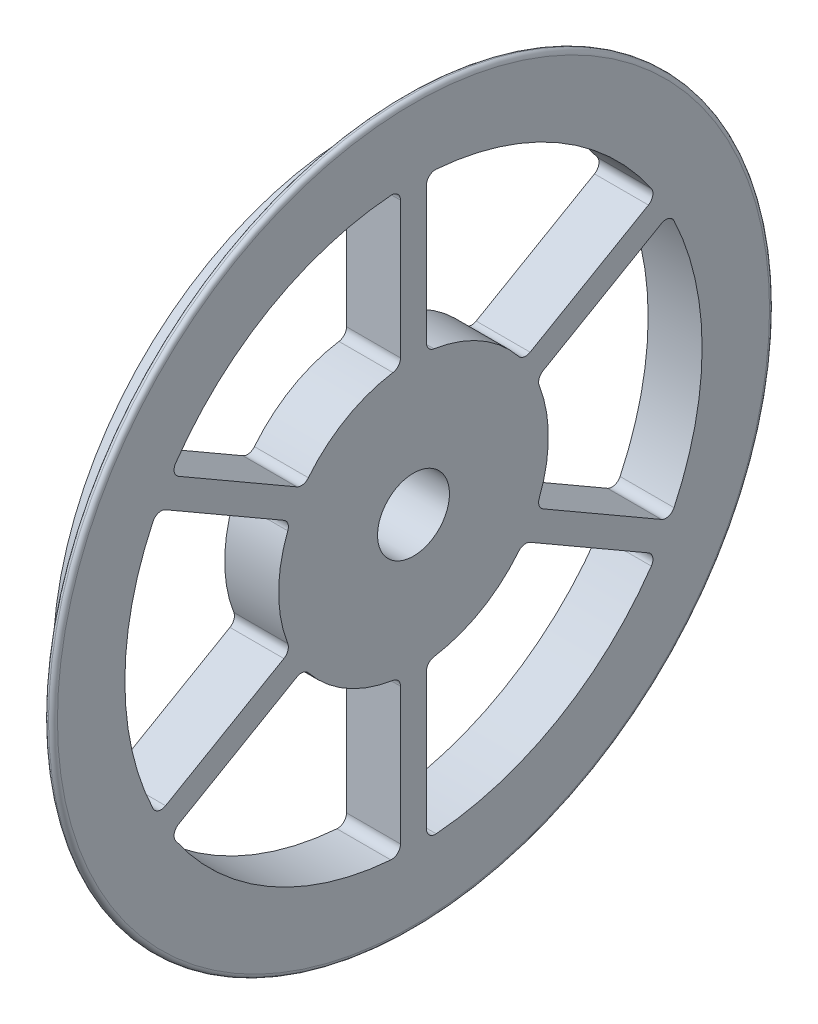
SolidWorks part; units mm, degrees
ref_plane "Front Plane" through (0, 0, 0) normal (0, 0, 1) x (1, 0, 0)
ref_plane "Top Plane" through (0, 0, 0) normal (0, 1, 0) x (1, 0, 0)
ref_plane "Right Plane" through (0, 0, 0) normal (1, 0, 0) x (0, 0, -1)
sketch "Sketch1" plane through (0, 0, 0) normal (0, 0, 1) x (1, 0, 0)
  line L2 (-3, 0) -> (-3, 38.05)
  line L5 (-3, 38.05) -> (2, 38.05)
  line L14 (2, 38.05) -> (2, 40.1)
  line L15 (2, 40.1) -> (3, 40.1)
  line L16 (3, 40.1) -> (3, 0)
  line L17 (3, 0) -> (-3, 0)
  dimension "D3" = 40.1
  dimension "D1" = 1
  dimension "D2" = 5
  dimension "D4" = 38.05
revolve "Revolve2" add sketch "Sketch1" angle 360 about L17
sketch "Sketch2" plane through (3, 0, 0) normal (-1, 0, 0) x (0, 0, 1)
  line L0 (0, 0) -> (13.6518, 0) construction
  line L1 (14.4156, 6.6562) -> (27.5718, 14.2519)
  line L2 (13.6518, 6.2152) -> (13.6518, -6.2152) construction
  line L3 (14.4156, -6.6562) -> (27.5718, -14.2519)
  line L4 (28.493, 14.7838) -> (28.493, -14.7838) construction
  line L5 (2.8868, 0) -> (13.6518, 6.2152) construction
  line L6 (2.8868, 0) -> (1.4434, 2.5) construction
  line L7 (1.4434, 2.5) -> (-1.4434, 2.5) construction
  line L8 (-1.4434, 2.5) -> (-2.8868, 0) construction
  line L9 (-2.8868, 0) -> (-1.4434, -2.5) construction
  line L10 (-1.4434, -2.5) -> (1.4434, -2.5) construction
  line L11 (1.4434, -2.5) -> (2.8868, 0) construction
  line L12 (13.6518, 0) -> (28.493, 0) construction
  line L13 (13.6518, -6.2152) -> (2.8868, 0) construction
  line L14 (12.9722, -9.1562) -> (26.1285, -16.7519)
  line L15 (1.4434, -15.8123) -> (1.4434, -31.0039)
  line L16 (-1.4434, -15.8123) -> (-1.4434, -31.0039)
  line L17 (-12.9722, -9.1562) -> (-26.1285, -16.7519)
  line L18 (-14.4156, -6.6562) -> (-27.5718, -14.2519)
  line L19 (-14.4156, 6.6562) -> (-27.5718, 14.2519)
  line L20 (-12.9722, 9.1562) -> (-26.1285, 16.7519)
  line L21 (-1.4434, 15.8123) -> (-1.4434, 31.0039)
  line L22 (1.4434, 15.8123) -> (1.4434, 31.0039)
  line L23 (12.9722, 9.1562) -> (26.1285, 16.7519)
  arc A0 (28.9745, 13.8163) -> (28.9745, -13.8163) centre (0, 0) cw
  circle A2 centre (0, 0) radius 2.5 construction
  arc A3 (13.9833, 5.4283) -> (13.9833, -5.4283) centre (0, 0) cw
  arc A4 (13.9833, -5.4283) -> (14.4156, -6.6562) centre (14.9156, -5.7901) ccw
  arc A5 (14.4156, 6.6562) -> (13.9833, 5.4283) centre (14.9156, 5.7901) ccw
  arc A6 (27.5718, -14.2519) -> (28.9745, -13.8163) centre (28.0718, -13.3859) ccw
  arc A7 (28.9745, 13.8163) -> (27.5718, 14.2519) centre (28.0718, 13.3859) ccw
  arc A8 (26.4525, -18.1845) -> (26.1285, -16.7519) centre (25.6285, -17.618) ccw
  arc A9 (26.4525, -18.1845) -> (2.5219, -32.0008) centre (0, 0) cw
  arc A10 (1.4434, -31.0039) -> (2.5219, -32.0008) centre (2.4434, -31.0039) ccw
  arc A11 (2.2907, -14.8241) -> (1.4434, -15.8123) centre (2.4434, -15.8123) ccw
  arc A12 (11.6927, -9.3958) -> (2.2907, -14.8241) centre (0, 0) cw
  arc A13 (12.9722, -9.1562) -> (11.6927, -9.3958) centre (12.4722, -10.0222) ccw
  arc A14 (-2.5219, -32.0008) -> (-1.4434, -31.0039) centre (-2.4434, -31.0039) ccw
  arc A15 (-2.5219, -32.0008) -> (-26.4525, -18.1845) centre (0, 0) cw
  arc A16 (-26.1285, -16.7519) -> (-26.4525, -18.1845) centre (-25.6285, -17.618) ccw
  arc A17 (-11.6927, -9.3958) -> (-12.9722, -9.1562) centre (-12.4722, -10.0222) ccw
  arc A18 (-2.2907, -14.8241) -> (-11.6927, -9.3958) centre (0, 0) cw
  arc A19 (-1.4434, -15.8123) -> (-2.2907, -14.8241) centre (-2.4434, -15.8123) ccw
  arc A20 (-28.9745, -13.8163) -> (-27.5718, -14.2519) centre (-28.0718, -13.3859) ccw
  arc A21 (-28.9745, -13.8163) -> (-28.9745, 13.8163) centre (0, 0) cw
  arc A22 (-27.5718, 14.2519) -> (-28.9745, 13.8163) centre (-28.0718, 13.3859) ccw
  arc A23 (-13.9833, 5.4283) -> (-14.4156, 6.6562) centre (-14.9156, 5.7901) ccw
  arc A24 (-13.9833, -5.4283) -> (-13.9833, 5.4283) centre (0, 0) cw
  arc A25 (-14.4156, -6.6562) -> (-13.9833, -5.4283) centre (-14.9156, -5.7901) ccw
  arc A26 (-26.4525, 18.1845) -> (-26.1285, 16.7519) centre (-25.6285, 17.618) ccw
  arc A27 (-26.4525, 18.1845) -> (-2.5219, 32.0008) centre (0, 0) cw
  arc A28 (-1.4434, 31.0039) -> (-2.5219, 32.0008) centre (-2.4434, 31.0039) ccw
  arc A29 (-2.2907, 14.8241) -> (-1.4434, 15.8123) centre (-2.4434, 15.8123) ccw
  arc A30 (-11.6927, 9.3958) -> (-2.2907, 14.8241) centre (0, 0) cw
  arc A31 (-12.9722, 9.1562) -> (-11.6927, 9.3958) centre (-12.4722, 10.0222) ccw
  arc A32 (2.5219, 32.0008) -> (1.4434, 31.0039) centre (2.4434, 31.0039) ccw
  arc A33 (2.5219, 32.0008) -> (26.4525, 18.1845) centre (0, 0) cw
  arc A34 (26.1285, 16.7519) -> (26.4525, 18.1845) centre (25.6285, 17.618) ccw
  arc A35 (11.6927, 9.3958) -> (12.9722, 9.1562) centre (12.4722, 10.0222) ccw
  arc A36 (2.2907, 14.8241) -> (11.6927, 9.3958) centre (0, 0) cw
  arc A37 (1.4434, 15.8123) -> (2.2907, 14.8241) centre (2.4434, 15.8123) ccw
  circle A39 centre (0, 0) radius 40.1 construction
  point P92 (0, 0)
  dimension "D5" = 5
  dimension "D2" = 15
  dimension "D3" = 1
  dimension "D1" = 30
  dimension "D4" = 8
  dimension "D6" = 6
extrude "Cut-Extrude2" cut sketch "Sketch2" along normal through all
fillet "Fillet1" radius 0.5 2 edges at (3, 0, -40.1) (2, 0, -40.1)
sketch "Sketch7" plane through (3, 0, 0) normal (1, 0, 0) x (0, 0, -1)
  circle A0 centre (0, 0) radius 4
  dimension "D1" = 8
extrude "Cut-Extrude5" cut sketch "Sketch7" against normal through all both and the other way through all
sketch "Sketch9" plane through (-3, 0, 0) normal (-1, 0, 0) x (0, 0, 1)
  circle A0 centre (0, 0) radius 34.1
  circle A1 centre (0, 0) radius 50
  dimension "D1" = 68.2
  dimension "D2" = 100
extrude "Cut-Extrude6" cut sketch "Sketch9" against normal offset from surface (4 mm away) 1 up to face at (2, 0, 39.6)
sketch "Sketch8" plane through (-3, 0, 0) normal (1, 0, 0) x (0, 0, -1)
  circle A0 centre (0, 0) radius 11.25
  dimension "D1" = 22.5
equation "\"SpokeWidth\"= 5"
equation "\"D5@Sketch2\" = \"SpokeWidth\""
equation "\"HubDiameter\"= 30"
equation "\"D2@Sketch2\"=\"HubDiameter\"/2"
equation "\"PulleyDiameter\"= 3in"
equation "\"PulleyWidth\"= 3.45in"
equation "\"RimWidth\"= 8"
equation "\"D4@Sketch2\"=\"RimWidth\""
